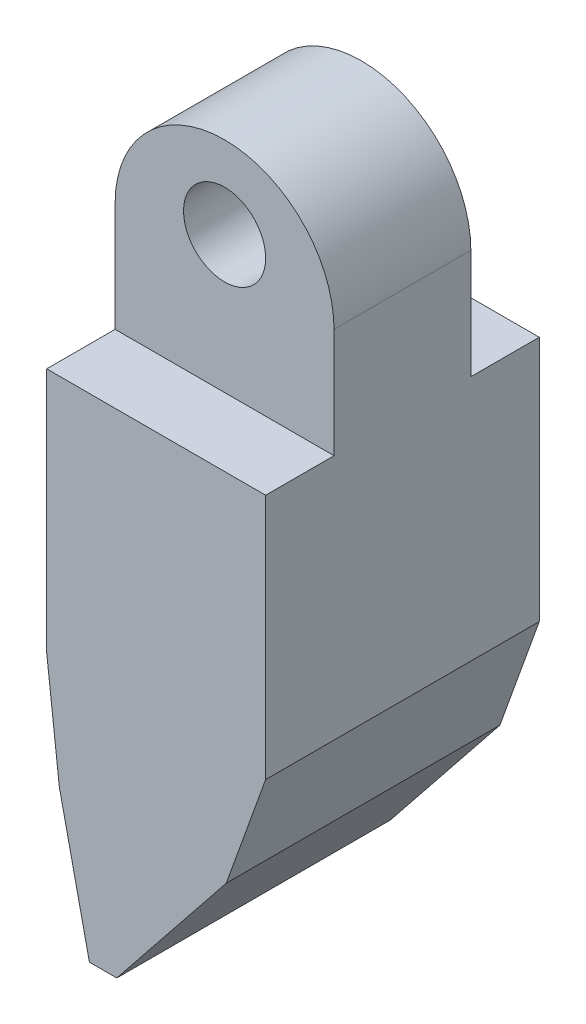
SolidWorks part; units mm, degrees
ref_plane "前视基准面" through (0, 0, 0) normal (0, 0, 1) x (1, 0, 0)
ref_plane "上视基准面" through (0, 0, 0) normal (0, 1, 0) x (1, 0, 0)
ref_plane "右视基准面" through (0, 0, 0) normal (1, 0, 0) x (0, 0, -1)
sketch "草图1" plane through (0, 0, 0) normal (0, 0, 1) x (1, 0, 0)
  line L0 (0, -65) -> (0, -85) construction
  line L1 (-20, 0) -> (20, 0)
  line L2 (-20, 0) -> (-20, -65)
  line L3 (-20, -65) -> (20, -65)
  line L4 (20, 0) -> (20, -65)
  line L5 (-20, 0) -> (20, -65) construction
  line L6 (-20, -65) -> (20, 0) construction
  line L7 (0, -85) -> (0, -110) construction
  line L8 (0, -85) -> (71.3073, -85) construction
  line L9 (0, -110) -> (73.1289, -110) construction
  line L10 (20, -65) -> (12.8, -85)
  line L11 (12.8, -85) -> (-7.2, -110)
  line L13 (12.2, -110) -> (37.7598, -110) construction
  line L14 (-12.2, -110) -> (0, -110)
  line L15 (-20, -65) -> (-17.7, -85)
  line L16 (-17.7, -85) -> (-12.2, -110)
  circle A0 centre (0, 0) radius 20
  point P7 (0, -32.5)
  point P14 (10.4702, -85)
  point P21 (-4.6657, -90.1382)
  dimension "D1" = 40
  dimension "D2" = 65
  dimension "D3" = 20
  dimension "D4" = 25
  dimension "D5" = 2.3
  dimension "D6" = 5.5
  dimension "D7" = 20
  dimension "D8" = 5
  dimension "D9" = 25
extrude "凸台-拉伸1" add sketch "草图1" along normal blind 50 contours L1 A0 | L1 A0 | A0 L2 L3 L4 | L15 L16 L14 L3 region at (0, 8.4883, 0) region at (0, -40.1519, 0) region at (0, -8.4883, 0) region at (-2.7295, -82.2597, 0)
sketch "草图2" plane through (0, 0, 0) normal (0, 0, -1) x (-1, 0, 0)
  line L1 (20, 0) -> (-20, 0)
  line L2 (20, 0) -> (20, -20)
  line L3 (20, -20) -> (-20, -20)
  line L4 (-20, 0) -> (-20, -20)
  line L5 (20, 0) -> (-20, -20) construction
  line L6 (20, -20) -> (-20, 0) construction
  line L8 (-20, 0) -> (-20, -65)
  line L9 (-20, -65) -> (-12.8, -85)
  line L10 (-20, -65) -> (-12.8, -85)
  line L11 (-12.8, -85) -> (7.2, -110)
  line L12 (7.2, -110) -> (12.2, -110)
  line L13 (12.2, -110) -> (17.7, -85)
  line L14 (17.7, -85) -> (20, -65)
  line L15 (20, -65) -> (20, 0)
  line L16 (-20, 0) -> (-20, -65) construction
  line L20 (7.2, -110) -> (12.2, -110) construction
  line L21 (12.2, -110) -> (17.7, -85) construction
  line L22 (17.7, -85) -> (20, -65) construction
  line L23 (20, -65) -> (20, 0) construction
  line L29 (-12.8, -85) -> (7.2, -110)
  arc A0 (0, -20) -> (12, -16) centre (0, 0) ccw
  arc A1 (20, 0) -> (-20, 0) centre (0, 0) ccw
  arc A2 (20, 0) -> (-20, 0) centre (0, 0) ccw
  arc A3 (-12, -16) -> (0, -20) centre (0, 0) ccw
  arc A4 (20, 0) -> (-19.5538, 4.2013) centre (0, 0) ccw
  point P9 (0, -10)
  arc M11 (20, 0) -> (-20, 0) centre (0, 0) ccw
  line M12 (-20, 0) -> (-20, -65)
  line M19 (20, -65) -> (20, 0)
  dimension "D2" = 20
  dimension "D1" = 0
extrude "切除-拉伸1" cut sketch "草图2" against normal blind 12.5 and the other way through all contours L1 A2 M11 | L3 L1 M19 M12 region at (0, -10, 0) region at (0, 8.4883, 0)
sketch "草图3" plane through (0, 0, 50) normal (0, 0, 1) x (1, 0, 0)
  line L3 (20, -20) -> (20, 0)
  line L4 (-20, -20) -> (20, -20)
  line L5 (-20, 0) -> (-20, -20)
  line L6 (20, -20) -> (20, 0)
  line L7 (-20, -20) -> (20, -20)
  line L8 (-20, 0) -> (-20, -20)
  arc A1 (20, 0) -> (-20, 0) centre (0, 0) ccw
  arc A2 (20, 0) -> (-20, 0) centre (0, 0) ccw
  dimension "D1" = 0
extrude "切除-拉伸2" cut sketch "草图3" against normal blind 12.5
sketch "草图4" plane through (0, 0, 12.5) normal (0, 0, -1) x (-1, 0, 0)
  line L0 (0, 0) -> (0, 5) construction
  circle A0 centre (0, 5) radius 7.5
  dimension "D2" = 15
  dimension "D1" = 5
extrude "切除-拉伸3" cut sketch "草图4" against normal through all
